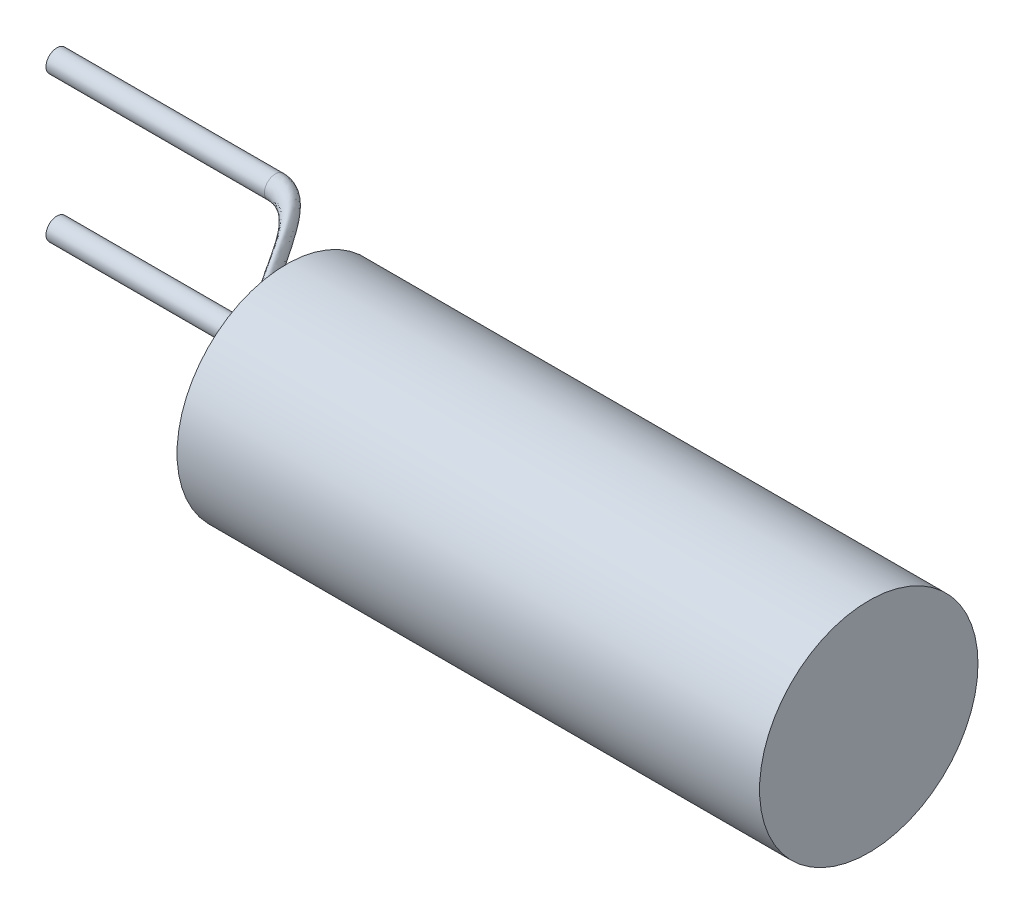
SolidWorks part; units mm, degrees
ref_plane "Спереди" through (0, 0, 0) normal (0, 0, 1) x (1, 0, 0)
ref_plane "Сверху" through (0, 0, 0) normal (0, 1, 0) x (1, 0, 0)
ref_plane "Справа" through (0, 0, 0) normal (1, 0, 0) x (0, 0, -1)
sketch "Эскиз1" plane through (0, 0, 0) normal (1, 0, 0) x (0, 0, -1)
  circle A0 centre (-1.5, 0) radius 1.5
  dimension "D1" = 1.5
  dimension "D2" = 3
extrude "Бобышка-Вытянуть1" add sketch "Эскиз1" along normal blind 4 and the other way blind 4
ref_plane "Плоскость4" through (-5.5, 0, 0) normal (1, 0, 0) x (0, 0, -1)
sketch "Эскиз2" plane through (-5.5, 0, 0) normal (1, 0, 0) x (0, 0, -1)
  line L0 (0, 1.65) -> (0, -1.65) construction
  line L1 (1.65, 0) -> (-1.65, 0) construction
  circle A0 centre (-0.15, 1) radius 0.15
  dimension "D2" = 0.3
  dimension "D3" = 1
  dimension "D1" = 0.15
extrude "Бобышка-Вытянуть2" add sketch "Эскиз2" against normal blind 3 separate body
sketch "Эскиз3" plane through (-4, 0, 0) normal (-1, 0, 0) x (0, 0, 1)
  circle A0 centre (1.5, 0.55) radius 0.15
  dimension "D3" = 0.3
  dimension "D1" = 0.55
  dimension "D2" = 1.5
extrude "Бобышка-Вытянуть3" add sketch "Эскиз3" along normal blind 0.1
pattern_linear "Линейный массив1" count 2 spacing 2 along (0, -1, 0) of "Бобышка-Вытянуть2"
loft "По сечениям1" add section face at (-5.5, 1, 0) section face at (-4.1, 0.55, 1.65) start constraint normal to profile start tangent length 1 end constraint normal to profile end tangent length 1 connector at (-5.5, 0.8577, 0.1026) connector at (-4.1, 0.4863, 1.3642)
pattern_linear "Линейный массив2" count 2 spacing 1.1 along (0, -1, 0) of "Бобышка-Вытянуть3"
loft "По сечениям2" add section face at (-5.5, -1, 0) section face at (-4.1, -0.55, 1.65) start constraint normal to profile start tangent length 1 end constraint normal to profile end tangent length 1 connector at (-5.5, -0.85, 0.1479) connector at (-4.1, -0.4455, 1.3923)
